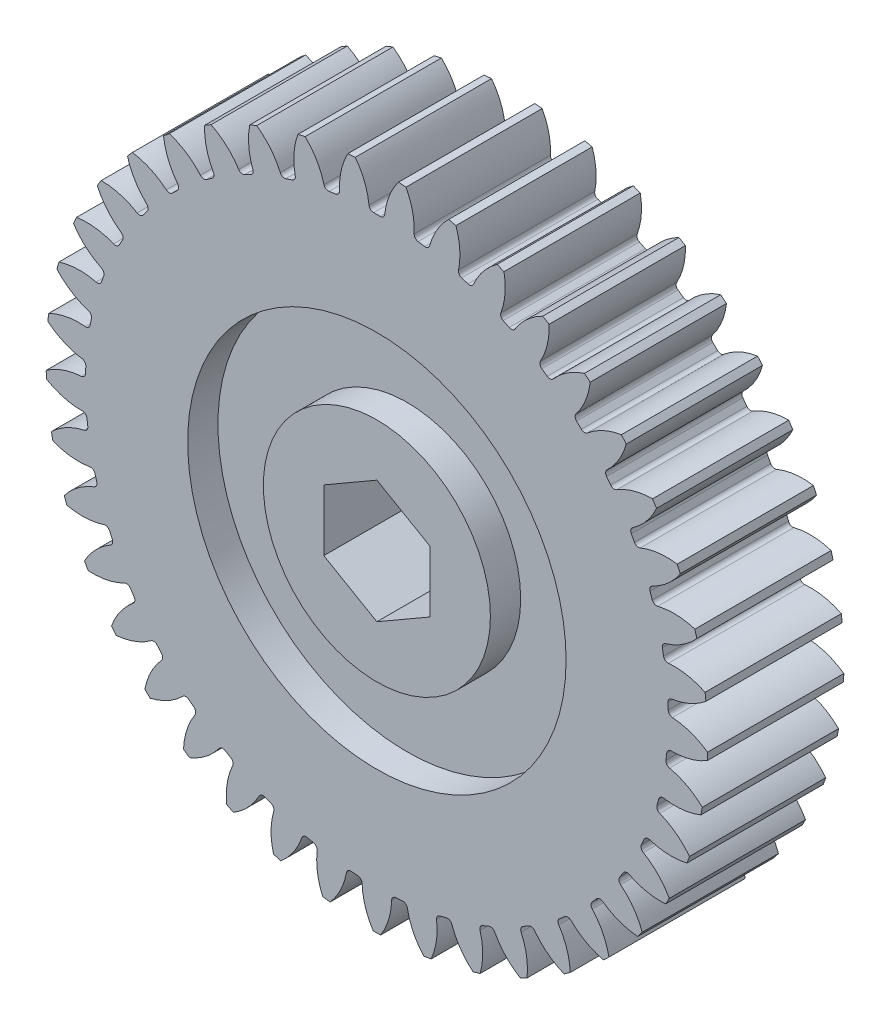
SolidWorks part; units mm, degrees
ref_plane "Ebene vorne" through (0, 0, 0) normal (0, 0, 1) x (1, 0, 0)
ref_plane "Ebene oben" through (0, 0, 0) normal (0, 1, 0) x (1, 0, 0)
ref_plane "Ebene rechts" through (0, 0, 0) normal (1, 0, 0) x (0, 0, -1)
sketch "Skizze1" plane through (0, 0, 0) normal (0, 0, 1) x (1, 0, 0)
  circle A0 centre (0, 0) radius 21.853
  dimension "D1" = 43.706
extrude "Aufsatz-Linear austragen1" add sketch "Skizze1" along normal mid plane 9
sketch "Skizze4" plane through (0, 0, 4.5) normal (0, 0, 1) x (1, 0, 0)
  circle A0 centre (0, 0) radius 7.5
  circle A1 centre (0, 0) radius 12.5
  dimension "D1" = 25
  dimension "D2" = 15
extrude "Schnitt-Linear austragen2" cut sketch "Skizze4" against normal blind 2
sketch "Skizze6" plane through (0, 0, 4.5) normal (0, 0, 1) x (1, 0, 0)
  line L0 (0, 0) -> (0, 21.853) construction
  line L1 (-0.2217, 19.25) -> (0.2217, 19.25)
  circle A0 centre (0, 0) radius 21.853 construction
  arc A1 (0.5201, 19.5188) -> (2.08, 22.5) centre (5.0554, 19.0445) cw
  arc A2 (-0.5201, 19.5188) -> (-2.08, 22.5) centre (-5.0554, 19.0445) ccw
  arc A3 (-2.08, 22.5) -> (2.08, 22.5) centre (0, 4.6206) cw
  arc A4 (0.2217, 19.25) -> (0.5201, 19.5188) centre (0.2217, 19.55) ccw
  arc A5 (-0.5201, 19.5188) -> (-0.2217, 19.25) centre (-0.2217, 19.55) ccw
  point P13 (0, 19.25)
  point P16 (0.5, 19.25)
  point P19 (-0.5, 19.25)
  dimension "D5" = 4.56
  dimension "D6" = 18
  dimension "D7" = 0.3
  dimension "D1" = 0.5
  dimension "D2" = 19.25
  dimension "D3" = 1.58
  dimension "D4" = 3.25
extrude "Schnitt-Linear austragen3" cut sketch "Skizze6" against normal through all
pattern_circular "Kreismuster1" count 41 over 360 about axis through (0, 0, 2.5) along (0, 0, 1) of "Schnitt-Linear austragen3" reverse direction yes
sketch "Skizze8" plane through (0, 0, -4.5) normal (0, 0, -1) x (-1, 0, 0)
  circle A0 centre (0, 0) radius 6
extrude "Aufsatz-Linear austragen2" add sketch "Skizze8" along normal blind 1 contours A0
sketch "Skizze7" plane through (0, 0, 4.5) normal (0, 0, 1) x (1, 0, 0)
  line L1 (0, 4.05) -> (-3.5074, 2.025)
  line L2 (-3.5074, 2.025) -> (-3.5074, -2.025)
  line L3 (-3.5074, -2.025) -> (0, -4.05)
  line L4 (0, -4.05) -> (3.5074, -2.025)
  line L5 (3.5074, -2.025) -> (3.5074, 2.025)
  line L6 (3.5074, 2.025) -> (0, 4.05)
  circle A0 centre (0, 0) radius 3.5074 construction
  dimension "D1" = 8.1
extrude "Schnitt-Linear austragen4" cut sketch "Skizze7" against normal through all
